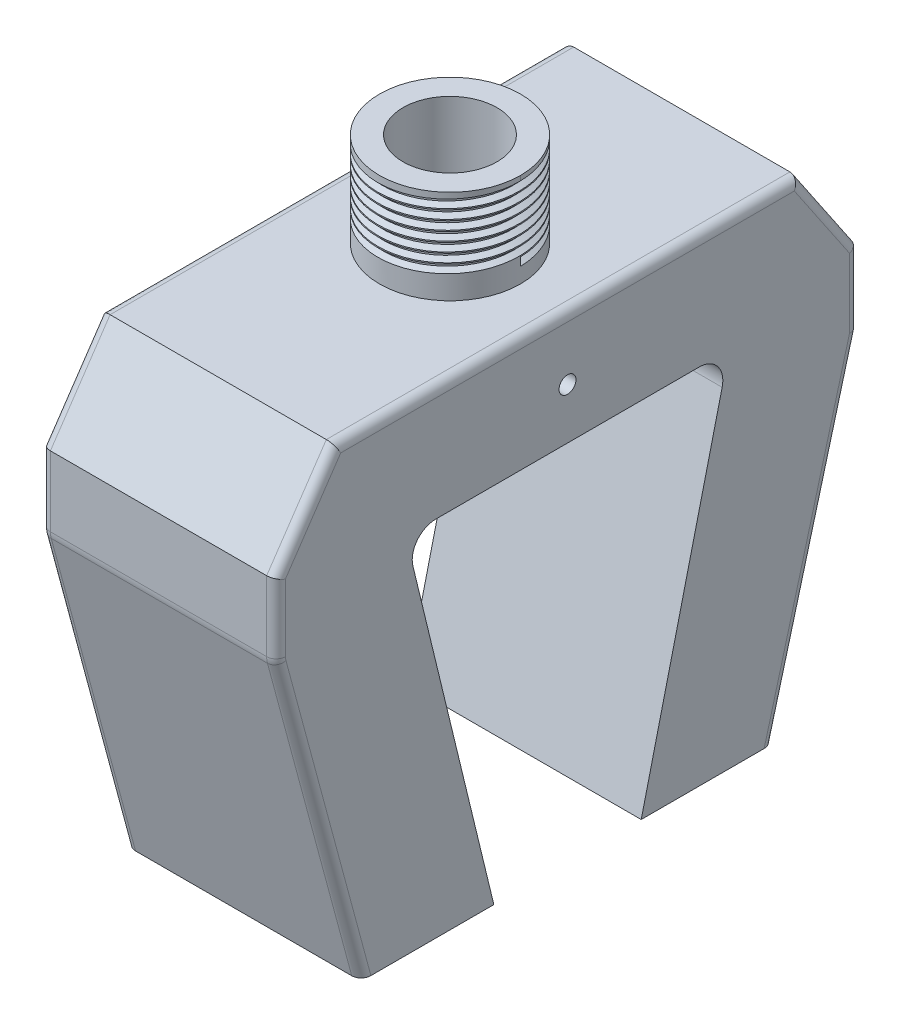
SolidWorks part; units mm, degrees
ref_plane "Front Plane" through (0, 0, 0) normal (0, 0, 1) x (1, 0, 0)
ref_plane "Top Plane" through (0, 0, 0) normal (0, 1, 0) x (1, 0, 0)
ref_plane "Right Plane" through (0, 0, 0) normal (1, 0, 0) x (0, 0, -1)
sketch "Sketch1" plane through (0, 0, 0) normal (1, 0, 0) x (0, 0, -1)
  line L0 (0, 108.6904) -> (0, -41.3096) construction
  line L1 (-72.5192, 212.2749) -> (138.1475, 212.2749) construction
  line L2 (-28.0385, 35.0948) -> (28.0385, 35.0948)
  line L3 (12, 87.0265) -> (22, 87.0265) construction
  line L4 (22, 87.0265) -> (22, 47.1887) construction
  line L5 (22, 47.1887) -> (17, 47.1887) construction
  line L6 (17, 47.1887) -> (17, 80.5878) construction
  line L7 (17, 80.5878) -> (12, 80.5878) construction
  line L8 (12, 80.5878) -> (12, 87.0265) construction
  line L9 (-49.3082, 59.3971) -> (49.3082, 59.3971)
  line L10 (49.3082, 59.3971) -> (62, 40.6619)
  line L11 (62, 40.6619) -> (62, 25.0807)
  line L12 (0, 112.6014) -> (0, 3.4775) construction
  line L13 (15.6748, -42.1029) -> (43.8994, -42.1029)
  line L14 (32.8976, 28.9164) -> (15.6748, -42.1029)
  line L15 (43.8994, -42.1029) -> (62, 25.0807)
  line L16 (-15.6748, -42.1029) -> (-43.8994, -42.1029)
  line L17 (-43.8994, -42.1029) -> (-61.8278, 24.4417)
  line L18 (-62, 40.6619) -> (-62, 25.7424)
  line L19 (-49.3082, 59.3971) -> (-62, 40.6619)
  line L20 (-32.8976, 28.9164) -> (-15.6748, -42.1029)
  arc A0 (-28.0385, 35.0948) -> (-32.8976, 28.9164) centre (-28.0385, 30.0948) ccw
  arc A1 (28.0385, 35.0948) -> (32.8976, 28.9164) centre (28.0385, 30.0948) cw
  arc A2 (-61.8278, 24.4417) -> (-62, 25.7424) centre (-57, 25.7424) cw
  point P8 (0, -41.3096)
  point P27 (0, 59.3971)
  point P28 (0, 35.0948)
  point P46 (-34.396, 35.0948)
  point P49 (34.396, 35.0948)
  point P52 (-62, 25.0807)
  dimension "D7" = 5
  dimension "D1" = 150
  dimension "D2" = 62
  dimension "D3" = 17
  dimension "D4" = 12
  dimension "D5" = 33.3992
  dimension "D6" = 101.5
extrude "Boss-Extrude1" add sketch "Sketch1" along normal blind 50
sketch "Sketch7" plane through (0, 59.3971, 0) normal (0, 1, 0) x (1, 0, 0)
  line L0 (0, 0) -> (50, 0) construction
  line L1 (50, 49.3082) -> (50, -49.3082) construction
  circle A0 centre (25, 0) radius 15
  dimension "D1" = 30
extrude "Boss-Extrude2" add sketch "Sketch7" along normal blind 20
thread "Thread2" pitch 2 method cut profile "Thread Profile2" start angle 0, offset 0, length 15, pitch 2, diameter 30
ref_plane "Plane5" through (10, 79.3971, 0) normal (0, 0, 1) x (-1, 0, 0)
sketch "Thread Profile2" plane through (10, 79.3971, 0) normal (0, 0, 1) x (-1, 0, 0)
  line L0 (0, 0) -> (0, 2) construction
  line L11 (0, 0) -> (0, 1.75)
  line L12 (0, 1.75) -> (-1.0825, 1.125)
  line L13 (-1.0825, 1.125) -> (-1.0825, 0.625)
  line L15 (-1.0825, 0.625) -> (0, 0)
  line L17 (-1.0825, 0.875) -> (0, 0.875) construction
  point P2 (0, 0)
  dimension "Pitch" = 2
  dimension "Profile_Angle" = 60
  dimension "Profile_Land" = 0.5
  dimension "Profile_Height" = 1.0825
sketch "Sketch13" plane through (0, 79.3971, 0) normal (0, 1, 0) x (1, 0, 0)
  line L0 (25, 15) -> (25, 0) construction
  circle A0 centre (25, 0) radius 15 construction
  circle A1 centre (25, 0) radius 15 construction
  circle A2 centre (25, 0) radius 10
  dimension "D1" = 20
extrude "Cut-Extrude2" cut sketch "Sketch13" against normal up to next
fillet "Fillet1" radius 2 16 edges at (50, 25.0864, 61.9568) (0, -8.8306, 52.8636) (0, 25.0864, 61.9568) (50, -8.5111, -52.9497) (50, 32.8713, -62) (50, 50.0295, -55.6541) (50, 33.2022, 62) (50, -8.8306, 52.8636) (50, 59.3971, 0) (50, 50.0295, 55.6541) (0, 33.2022, 62) (0, 50.0295, 55.6541) (0, 59.3971, 0) (0, 50.0295, -55.6541) (0, 32.8713, -62) (0, -8.5111, -52.9497)
sketch "Sketch14" plane through (0, 0, 0) normal (-1, 0, 0) x (0, 0, 1)
  circle A0 centre (0, 45.872) radius 1.8
  dimension "D1" = 3.6
extrude "Cut-Extrude3" cut sketch "Sketch14" against normal through all
